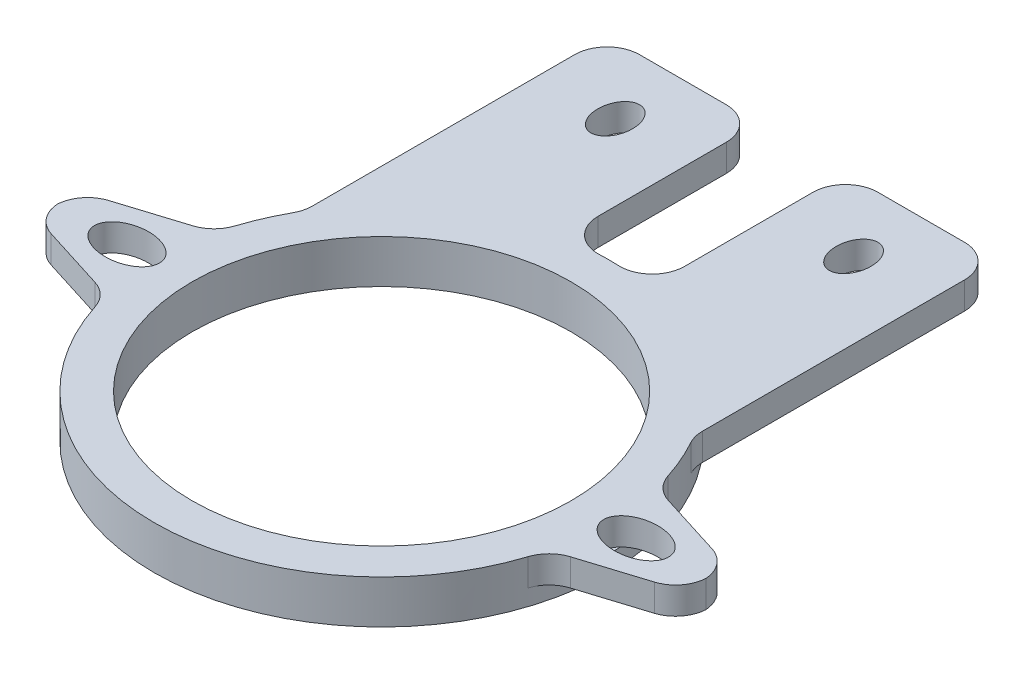
SolidWorks part; units mm, degrees
ref_plane "Front Plane" through (0, 0, 0) normal (0, 0, 1) x (1, 0, 0)
ref_plane "Top Plane" through (0, 0, 0) normal (0, 1, 0) x (1, 0, 0)
ref_plane "Right Plane" through (0, 0, 0) normal (1, 0, 0) x (0, 0, -1)
sketch "Sketch1" plane through (0, 0, 0) normal (0, 1, 0) x (1, 0, 0)
  circle A0 centre (0, 0) radius 17.5
  circle A1 centre (0, 0) radius 21
  dimension "D1" = 35
  dimension "D2" = 42
extrude "Boss-Extrude1" add sketch "Sketch1" along normal blind 4
sketch "Sketch2" plane through (0, 4, 0) normal (0, 1, 0) x (1, 0, 0)
  line L0 (-20.3961, 5) -> (-29.9355, 2)
  line L1 (-29.9355, 2) -> (-29.9355, -2)
  line L2 (-29.9355, -2) -> (-20.3961, -5)
  line L3 (-20.3961, -5) -> (-20.3961, 5)
  line L4 (0, 27.4019) -> (0, -24.9255) construction
  line L5 (20.3961, -5) -> (20.3961, 5)
  line L6 (29.9355, -2) -> (20.3961, -5)
  line L7 (29.9355, 2) -> (29.9355, -2)
  line L8 (20.3961, 5) -> (29.9355, 2)
  line L9 (-18, 10.8167) -> (-18, 38.8167)
  line L10 (-18, 38.8167) -> (-4, 38.8167)
  line L11 (-4, 38.8167) -> (-4, 20.6155)
  line L12 (-4, 20.6155) -> (-18, 10.8167)
  line L13 (4, 20.6155) -> (18, 10.8167)
  line L14 (4, 38.8167) -> (4, 20.6155)
  line L15 (18, 38.8167) -> (4, 38.8167)
  line L16 (18, 10.8167) -> (18, 38.8167)
  circle A0 centre (0, 0) radius 21 construction
  point P4 (-20.3961, 0)
  point P9 (-29.9355, 0)
  dimension "D1" = 10
  dimension "D2" = 4
  dimension "D3" = 10
  dimension "D4" = 28
  dimension "D5" = 14
  dimension "D6" = 4
extrude "Boss-Extrude2" add sketch "Sketch2" against normal blind 2.5
sketch "Sketch3" plane through (0, 4, 0) normal (0, 1, 0) x (1, 0, 0)
  line L0 (-4, 38.8167) -> (-18, 38.8167) construction
  line L1 (18, 38.8167) -> (4, 38.8167) construction
  line L2 (26.5, 0) -> (29.9355, 0) construction
  line L3 (29.9355, -2) -> (29.9355, 2) construction
  line L4 (-26.5, 0) -> (-29.9355, 0) construction
  line L5 (-29.9355, 2) -> (-29.9355, -2) construction
  ellipse E0 centre (-11, 32.5667) end of major axis (-11, 34.8167) minor radius 1.6
  ellipse E1 centre (11, 32.5667) end of major axis (11, 34.8167) minor radius 1.6
  ellipse E2 centre (-23.5, 0) end of major axis (-20.5, 0) minor radius 2
  ellipse E3 centre (23.5, 0) end of major axis (20.5, 0) minor radius 2
  point P20 (-11, 38.8167)
  point P22 (11, 38.8167)
  point P38 (0, 0)
  dimension "D1" = 3.2
  dimension "D2" = 3.2
  dimension "D3" = 4.5
  dimension "D4" = 4.5
  dimension "D5" = 4
  dimension "D6" = 4
  dimension "D7" = 4
  dimension "D8" = 6
  dimension "D9" = 47
  dimension "D11" = 6
  dimension "D12" = 4
extrude "Cut-Extrude1" cut sketch "Sketch3" against normal blind 2.5
fillet "Fillet1" radius 3 16 edges at (-18, 2.75, -10.8167) (-18, 2.75, -38.8167) (-4, 2.75, -38.8167) (-4, 2.75, -20.6155) (4, 2.75, -20.6155) (4, 2.75, -38.8167) (18, 2.75, -38.8167) (18, 2.75, -10.8167) (20.3961, 2.75, -5) (29.9355, 2.75, -2) (29.9355, 2.75, 2) (20.3961, 2.75, 5) (-20.3961, 2.75, 5) (-29.9355, 2.75, 2) (-29.9355, 2.75, -2) (-20.3961, 2.75, -5)
